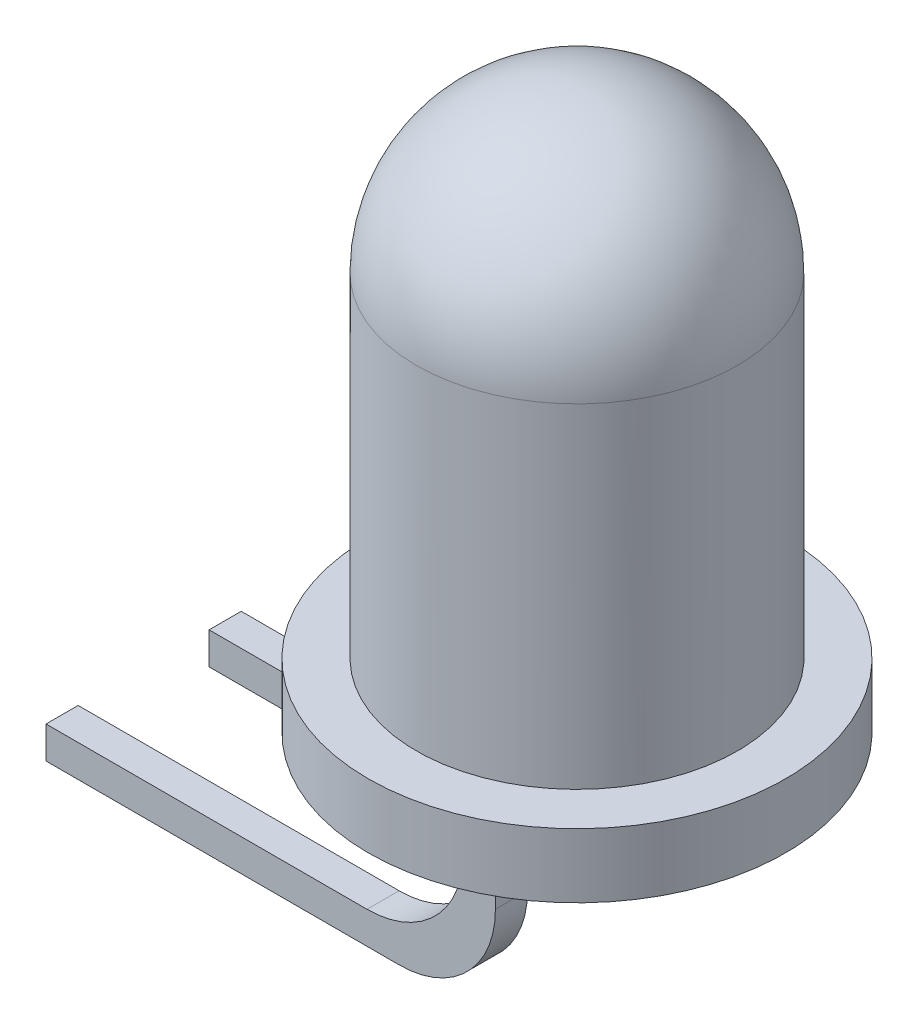
SolidWorks part; units mm, degrees
ref_plane "Front" through (0, 0, 0) normal (0, 0, 1) x (1, 0, 0)
ref_plane "Top" through (0, 0, 0) normal (0, 1, 0) x (1, 0, 0)
ref_plane "Right" through (0, 0, 0) normal (1, 0, 0) x (0, 0, -1)
sketch "Эскиз1" plane through (0, 0, 0) normal (1, 0, 0) x (0, 0, -1)
  line L0 (0, -2.6033) -> (0, 12.5474) construction
  line L1 (-3.25, 0) -> (0, 0)
  line L2 (-3.25, 0) -> (-3.25, 1)
  line L3 (-3.25, 1) -> (0, 1)
  line L4 (-2.5, 1) -> (-2.5, 6.2)
  line L5 (0, 8.7) -> (0, 0)
  arc A0 (-2.5, 6.2) -> (0, 8.7) centre (0, 6.2) cw
  dimension "D3" = 1
  dimension "D1" = 8.7
  dimension "D2" = 5
  dimension "D4" = 6.5
revolve "Повернуть1" add sketch "Эскиз1" angle 360 about L0 region at (0, 0.5, 1.625) region at (0, 4.6035, 1.1982)
sketch "Эскиз2" plane through (0, 0, 0) normal (0, 0, 1) x (1, 0, 0)
  line L0 (0.25, 0) -> (0.25, -1.5)
  line L1 (-3.25, 0) -> (3.25, 0) construction
  line L2 (-1.25, -3) -> (-6.75, -3)
  line L3 (-0.25, 0) -> (-0.25, -1)
  line L4 (-1.75, -2.5) -> (-6.75, -2.5)
  line L5 (-6.75, -2.5) -> (-6.75, -3)
  line L6 (0.25, 0) -> (0.25, -3) construction
  line L7 (0.25, -3) -> (-6.75, -3) construction
  line L8 (-0.25, 0) -> (-0.25, -2.5) construction
  line L9 (-0.25, -2.5) -> (-6.75, -2.5) construction
  line L10 (-0.25, 0) -> (0.25, 0)
  arc A0 (0.25, -1.5) -> (-1.25, -3) centre (-1.25, -1.5) cw
  arc A1 (-0.25, -1) -> (-1.75, -2.5) centre (-1.75, -1) cw
  point P12 (0.25, -3)
  dimension "D5" = 1.5
  dimension "D1" = 3
  dimension "D2" = 7
  dimension "D3" = 0.25
  dimension "D4" = 0.5
extrude "Бобышка-Вытянуть1" add sketch "Эскиз2" along normal mid plane 3.04
sketch "Эскиз3" plane through (0, -3, 0) normal (0, -1, 0) x (1, 0, 0)
  line L0 (0.25, 1.02) -> (-6.75, 1.02)
  line L1 (0.25, 1.52) -> (0.25, -1.52) construction
  line L2 (-6.75, 1.52) -> (-6.75, -1.52) construction
  line L3 (-6.75, 1.02) -> (-6.75, 1.52)
  line L4 (-6.75, 1.52) -> (0.25, 1.52)
  line L5 (0.25, 1.52) -> (0.25, 1.02)
  line L6 (-6.75, -1.02) -> (0.25, -1.02)
  line L7 (0.25, -1.02) -> (0.25, -1.52)
  line L8 (-1.25, -1.52) -> (0.25, -1.52) construction
  line L9 (0.25, -1.52) -> (-6.75, -1.52)
  line L10 (-6.75, -1.52) -> (-6.75, -1.02)
  line L11 (-6.75, 1.02) -> (-6.75, -1.02)
  line L12 (0.25, 1.02) -> (0.25, -1.02)
  line M4 (-1.25, -1.52) -> (-1.25, 1.52)
  line M6 (-6.75, 1.52) -> (-6.75, -1.52)
  dimension "D1" = 0.5
  dimension "D2" = 0.5
extrude "Вырез-Вытянуть1" cut sketch "Эскиз3" against normal up to surface (3 mm away) contours L6 L0 M6 M4 | L12 L0 L6 M4 region at (-0.5, -3, 0) region at (-4, -3, 0) up to face at (0, 0, 0)
